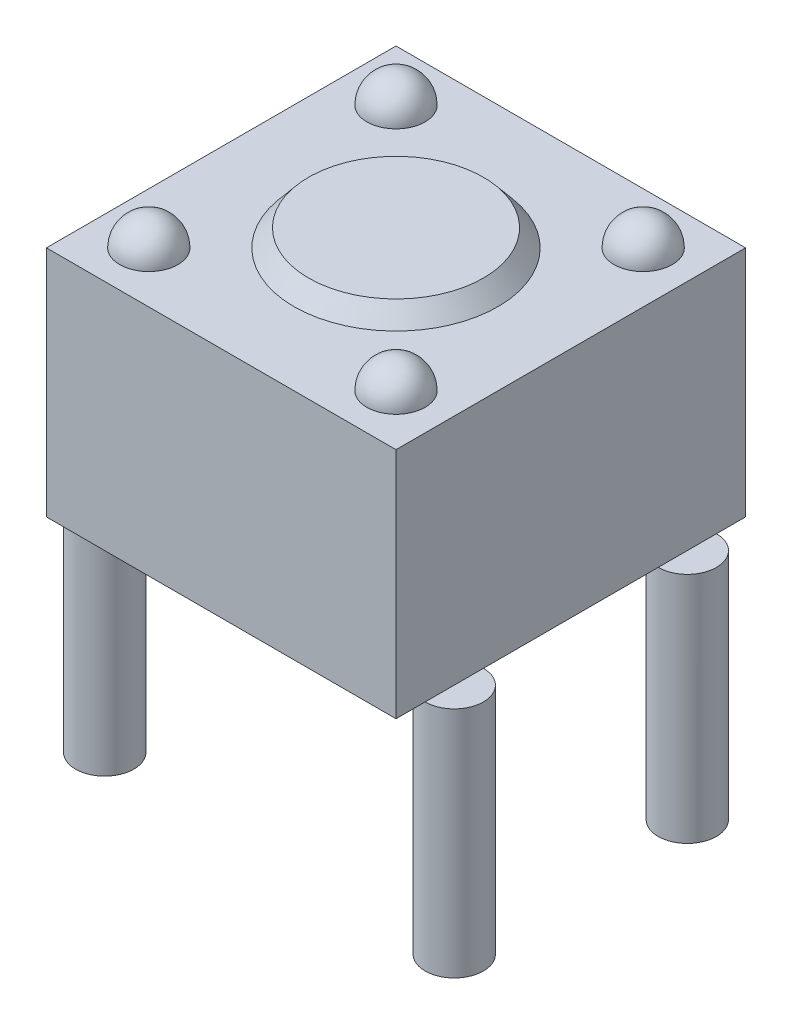
SolidWorks part; units mm, degrees
ref_plane "Front Plane" through (0, 0, 0) normal (0, 0, 1) x (1, 0, 0)
ref_plane "Top Plane" through (0, 0, 0) normal (0, 1, 0) x (1, 0, 0)
ref_plane "Right Plane" through (0, 0, 0) normal (1, 0, 0) x (0, 0, -1)
sketch "Sketch1" plane through (0, 0, 0) normal (0, 1, 0) x (1, 0, 0)
  line L0 (-3, 3) -> (3, -3) construction
  line L1 (-3, 3) -> (3, 3)
  line L2 (-3, 3) -> (-3, -3)
  line L3 (-3, -3) -> (3, -3)
  line L4 (3, 3) -> (3, -3)
  dimension "D1" = 6
extrude "Boss-Extrude1" add sketch "Sketch1" along normal blind 4
sketch "Sketch2" plane through (0, 4, 0) normal (0, 1, 0) x (1, 0, 0)
  circle A0 centre (0, 0) radius 1.75
  dimension "D1" = 3.5
extrude "Boss-Extrude2" add sketch "Sketch2" along normal blind 4.3 from surface starting at plane "Top Plane"
sketch "Sketch3" plane through (0, 0, 0) normal (1, 0, 0) x (0, 0, -1)
  line L0 (-1.75, 4.3) -> (-1.75, 4) construction
  line L1 (-1.75, 4.3) -> (-1.75, 4)
  line L2 (1.75, 4.3) -> (-1.75, 4.3) construction
  line L3 (-1.5, 4.3) -> (-1.75, 4.3)
  line L4 (-1.75, 4) -> (-1.5, 4.3)
  line L5 (0, 3.85) -> (0, -3.85) construction
  line L6 (0, 8.3744) -> (0, 7.4714) construction
  dimension "D1" = 1.5
revolve "Cut-Revolve1" cut sketch "Sketch3" angle 360 about L6
sketch "Sketch4" plane through (0, 4, 0) normal (0, 1, 0) x (1, 0, 0)
  line L0 (0, 0) -> (-2.1213, 2.1213) construction
  line L1 (-3.85, 0) -> (3.85, 0) construction
  circle A0 centre (-2.1213, 2.1213) radius 0.5
  circle A1 centre (2.1213, 2.1213) radius 0.5
  circle A2 centre (2.1213, -2.1213) radius 0.5
  circle A3 centre (-2.1213, -2.1213) radius 0.5
  point P15 (0, 0)
  dimension "D1" = 1
  dimension "D2" = 45
  dimension "D3" = 3
  dimension "D4" = 4
extrude "Boss-Extrude3" add sketch "Sketch4" along normal blind 0.5
fillet "Fillet1" radius 0.5 4 edges at (2.1213, 4.5, -1.6213) (2.1213, 4.5, 2.6213) (-2.1213, 4.5, 2.6213) (-2.1213, 4.5, -1.6213)
sketch "Sketch5" plane through (0, 0, 0) normal (0, 1, 0) x (1, 0, 0)
  line L0 (3, -3) -> (3, 3) construction
  line L1 (-3.85, 0) -> (3.85, 0) construction
  line L2 (0.9915, 0) -> (1.5091, 0) construction
  line L3 (0, -1.3995) -> (0, -0.7063) construction
  line L4 (0, -3.3) -> (0, 3.3) construction
  circle A0 centre (3, -2) radius 0.5
  circle A1 centre (3, 2) radius 0.5
  circle A2 centre (-3, 2) radius 0.5
  circle A3 centre (-3, -2) radius 0.5
  dimension "D1" = 1
  dimension "D2" = 2
extrude "Boss-Extrude4" add sketch "Sketch5" against normal blind 4
